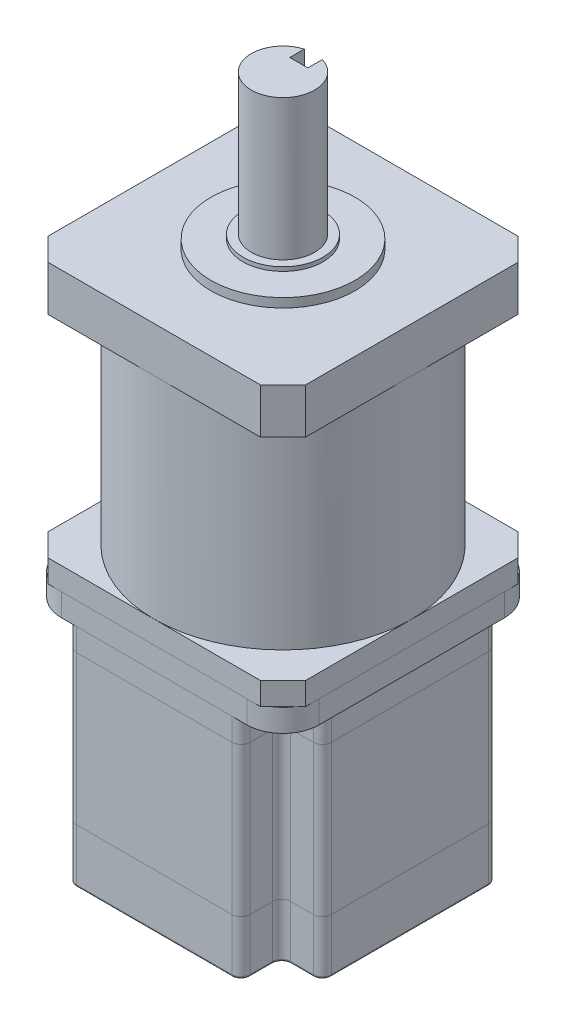
SolidWorks part; units mm, degrees
ref_plane "Front Plane" through (0, 0, 0) normal (0, 0, 1) x (1, 0, 0)
ref_plane "Top Plane" through (0, 0, 0) normal (0, 1, 0) x (1, 0, 0)
ref_plane "Right Plane" through (0, 0, 0) normal (1, 0, 0) x (0, 0, -1)
sketch "Sketch1" plane through (0, 0, 0) normal (0, 1, 0) x (1, 0, 0)
  circle A0 centre (0, 0) radius 28.5
  dimension "D1" = 57
extrude "Boss-Extrude1" add sketch "Sketch1" along normal blind 56.65
sketch "Sketch2" plane through (0, 0, 0) normal (0, -1, 0) x (1, 0, 0)
  line L1 (-28.5, 28.5) -> (28.5, 28.5)
  line L2 (-28.5, 28.5) -> (-28.5, -28.5)
  line L3 (-28.5, -28.5) -> (28.5, -28.5)
  line L4 (28.5, 28.5) -> (28.5, -28.5)
  line L5 (-28.5, 28.5) -> (28.5, -28.5) construction
  line L6 (-28.5, -28.5) -> (28.5, 28.5) construction
  point P0 (0, 0)
  dimension "D1" = 57
  dimension "D2" = 57
extrude "Boss-Extrude2" add sketch "Sketch2" along normal blind 5 separate body
chamfer "Chamfer1" distance 5 angle 45 4 edges at (28.5, -2.5, -28.5) (-28.5, -2.5, -28.5) (28.5, -2.5, 28.5) (-28.5, -2.5, 28.5)
sketch "Sketch3" plane through (0, -5, 0) normal (0, -1, 0) x (1, 0, 0)
  line L1 (-28.5, -28.5) -> (28.5, -28.5)
  line L2 (-28.5, -28.5) -> (-28.5, 28.5)
  line L3 (-28.5, 28.5) -> (28.5, 28.5)
  line L4 (28.5, -28.5) -> (28.5, 28.5)
  line L5 (-28.5, -28.5) -> (28.5, 28.5) construction
  line L6 (-28.5, 28.5) -> (28.5, -28.5) construction
  point P0 (0, 0)
  dimension "D1" = 57
  dimension "D2" = 57
extrude "Boss-Extrude3" add sketch "Sketch3" along normal blind 5 separate body
sketch "Sketch4" plane through (0, -10, 0) normal (0, -1, 0) x (1, 0, 0)
  line L0 (0, 28.5) -> (0, -28.5) construction
  line L1 (23.5, 28.5) -> (-23.5, 28.5) construction
  line L2 (-23.5, -28.5) -> (23.5, -28.5) construction
  line L3 (-28.5, 0) -> (28.5, 0) construction
  line L4 (-28.5, 23.5) -> (-28.5, -23.5) construction
  line L5 (28.5, -23.5) -> (28.5, 23.5) construction
  circle A0 centre (-23.5, 23.5) radius 2.5
  circle A1 centre (23.5, 23.5) radius 2.5
  circle A2 centre (23.5, -23.5) radius 2.5
  circle A3 centre (-23.5, -23.5) radius 2.5
  dimension "D1" = 5
  dimension "D2" = 5
  dimension "D3" = 5
  dimension "D4" = 5
  dimension "D7" = 23.5
  dimension "D8" = 23.5
  dimension "D9" = 23.5
  dimension "D10" = 23.5
  dimension "D11" = 23.5
  dimension "D12" = 23.5
  dimension "D5" = 23.5
  dimension "D6" = 23.5
extrude "Cut-Extrude1" cut sketch "Sketch4" against normal blind 15
sketch "Sketch6" plane through (0, -10, 0) normal (0, -1, 0) x (1, 0, 0)
  line L0 (28.5, 28.5) -> (-28.5, 28.5) construction
  line L1 (-19.2, 28.5) -> (19.2, 28.5)
  line L2 (-28.2, 19.5) -> (-28.2, -19.25)
  line L3 (-19.2, -28.25) -> (19.2, -28.25)
  line L4 (28.2, 19.5) -> (28.2, -19.25)
  line L9 (-28.2, 19.5) -> (-19.2, 19.5)
  line L10 (-19.2, 28.5) -> (-19.2, 19.5)
  line L11 (28.2, 19.5) -> (19.2, 19.5)
  line L12 (19.2, 28.5) -> (19.2, 19.5)
  line L15 (28.2, -19.25) -> (19.2, -19.25)
  line L16 (19.2, -28.25) -> (19.2, -19.25)
  line L19 (-28.2, -19.25) -> (-19.2, -19.25)
  line L20 (-19.2, -28.25) -> (-19.2, -19.25)
  dimension "D1" = 9
  dimension "D2" = 9
  dimension "D3" = 9
  dimension "D4" = 9
  dimension "D5" = 9
  dimension "D6" = 9
  dimension "D7" = 9
  dimension "D8" = 9
extrude "Boss-Extrude4" add sketch "Sketch6" along normal blind 5 separate body
sketch "Sketch7" plane through (0, -15, 0) normal (0, -1, 0) x (1, 0, 0)
  line L12 (19.2, 19.5) -> (19.2, 28.5)
  line L13 (19.2, 28.5) -> (-19.2, 28.5)
  line L14 (-19.2, 28.5) -> (-19.2, 19.5)
  line L15 (-19.2, 19.5) -> (-28.2, 19.5)
  line L16 (-28.2, 19.5) -> (-28.2, -19.25)
  line L17 (-28.2, -19.25) -> (-19.2, -19.25)
  line L18 (-19.2, -19.25) -> (-19.2, -28.25)
  line L19 (-19.2, -28.25) -> (19.2, -28.25)
  line L20 (19.2, -28.25) -> (19.2, -19.25)
  line L21 (19.2, -19.25) -> (28.2, -19.25)
  line L22 (28.2, -19.25) -> (28.2, 19.5)
  line L23 (28.2, 19.5) -> (19.2, 19.5)
  line L24 (19.2, 19.5) -> (19.2, 28.5)
  line L25 (19.2, 28.5) -> (-19.2, 28.5)
  line L26 (-19.2, 28.5) -> (-19.2, 19.5)
  line L27 (-19.2, 19.5) -> (-28.2, 19.5)
  line L28 (-28.2, 19.5) -> (-28.2, -19.25)
  line L29 (-28.2, -19.25) -> (-19.2, -19.25)
  line L30 (-19.2, -19.25) -> (-19.2, -28.25)
  line L31 (-19.2, -28.25) -> (19.2, -28.25)
  line L32 (19.2, -28.25) -> (19.2, -19.25)
  line L33 (19.2, -19.25) -> (28.2, -19.25)
  line L34 (28.2, -19.25) -> (28.2, 19.5)
  line L35 (28.2, 19.5) -> (19.2, 19.5)
  dimension "D1" = 0
extrude "Boss-Extrude5" add sketch "Sketch7" along normal blind 33 separate body
sketch "Sketch8" plane through (0, -48, 0) normal (0, -1, 0) x (1, 0, 0)
  line L12 (28.2, 19.5) -> (19.2, 19.5)
  line L13 (19.2, 19.5) -> (19.2, 28.5)
  line L14 (19.2, 28.5) -> (-19.2, 28.5)
  line L15 (-19.2, 28.5) -> (-19.2, 19.5)
  line L16 (-19.2, 19.5) -> (-28.2, 19.5)
  line L17 (-28.2, 19.5) -> (-28.2, -19.25)
  line L18 (-28.2, -19.25) -> (-19.2, -19.25)
  line L19 (-19.2, -19.25) -> (-19.2, -28.25)
  line L20 (-19.2, -28.25) -> (19.2, -28.25)
  line L21 (19.2, -28.25) -> (19.2, -19.25)
  line L22 (19.2, -19.25) -> (28.2, -19.25)
  line L23 (28.2, -19.25) -> (28.2, 19.5)
  line L24 (28.2, 19.5) -> (19.2, 19.5)
  line L25 (19.2, 19.5) -> (19.2, 28.5)
  line L26 (19.2, 28.5) -> (-19.2, 28.5)
  line L27 (-19.2, 28.5) -> (-19.2, 19.5)
  line L28 (-19.2, 19.5) -> (-28.2, 19.5)
  line L29 (-28.2, 19.5) -> (-28.2, -19.25)
  line L30 (-28.2, -19.25) -> (-19.2, -19.25)
  line L31 (-19.2, -19.25) -> (-19.2, -28.25)
  line L32 (-19.2, -28.25) -> (19.2, -28.25)
  line L33 (19.2, -28.25) -> (19.2, -19.25)
  line L34 (19.2, -19.25) -> (28.2, -19.25)
  line L35 (28.2, -19.25) -> (28.2, 19.5)
  dimension "D1" = 0
extrude "Boss-Extrude6" add sketch "Sketch8" along normal blind 12 separate body
fillet "Fillet1" radius 2 12 edges at (19.2, -12.5, -19.25) (19.2, -12.5, -28.25) (-19.2, -12.5, -28.25) (-19.2, -12.5, -19.25) (-28.2, -12.5, -19.25) (-28.2, -12.5, 19.5) (-19.2, -12.5, 19.5) (-19.2, -12.5, 28.5) (28.2, -12.5, -19.25) (19.2, -12.5, 19.5) (19.2, -12.5, 28.5) (28.2, -12.5, 19.5)
fillet "Fillet2" radius 2 12 edges at (-19.2, -31.5, -28.25) (-19.2, -31.5, -19.25) (-28.2, -31.5, -19.25) (-28.2, -31.5, 19.5) (-19.2, -31.5, 19.5) (-19.2, -31.5, 28.5) (19.2, -31.5, 28.5) (19.2, -31.5, 19.5) (28.2, -31.5, 19.5) (28.2, -31.5, -19.25) (19.2, -31.5, -19.25) (19.2, -31.5, -28.25)
fillet "Fillet3" radius 2 12 edges at (-28.2, -54, 19.5) (-19.2, -54, 19.5) (-19.2, -54, 28.5) (19.2, -54, 28.5) (19.2, -54, 19.5) (28.2, -54, 19.5) (28.2, -54, -19.25) (19.2, -54, -19.25) (19.2, -54, -28.25) (-19.2, -54, -28.25) (-19.2, -54, -19.25) (-28.2, -54, -19.25)
fillet "Fillet4" radius 0.5 24 edges at (-19.7858, -60, 20.0858) (-19.2, -60, 24) (-18.6142, -60, 27.9142) (0, -60, 28.5) (18.6142, -60, 27.9142) (19.2, -60, 24) (19.7858, -60, 20.0858) (23.7, -60, 19.5) (27.6142, -60, 18.9142) (28.2, -60, 0.125) (27.6142, -60, -18.6642) (23.7, -60, -19.25) (19.7858, -60, -19.8358) (19.2, -60, -23.75) (18.6142, -60, -27.6642) (0, -60, -28.25) (-18.6142, -60, -27.6642) (-19.2, -60, -23.75) (-19.7858, -60, -19.8358) (-23.7, -60, -19.25) (-27.6142, -60, -18.6642) (-28.2, -60, 0.125) (-27.6142, -60, 18.9142) (-23.7, -60, 19.5)
fillet "Fillet5" radius 8 4 edges at (-28.5, -7.5, -28.5) (-28.5, -7.5, 28.5) (28.5, -7.5, -28.5) (28.5, -7.5, 28.5)
sketch "Sketch9" plane through (0, 56.65, 0) normal (0, 1, 0) x (1, 0, 0)
  circle A0 centre (0, 0) radius 15.95
  dimension "D1" = 31.9
extrude "Boss-Extrude7" add sketch "Sketch9" along normal blind 2
sketch "Sketch10" plane through (0, 58.65, 0) normal (0, 1, 0) x (1, 0, 0)
  circle A0 centre (0, 0) radius 8.85
  dimension "D1" = 17.7
extrude "Boss-Extrude8" add sketch "Sketch10" along normal blind 0.9 separate body
sketch "Sketch11" plane through (0, 59.55, 0) normal (0, 1, 0) x (1, 0, 0)
  circle A0 centre (0, 0) radius 7
  dimension "D1" = 14
extrude "Boss-Extrude9" add sketch "Sketch11" along normal blind 31.1 separate body
sketch "Sketch12" plane through (0, 90.65, 0) normal (0, 1, 0) x (1, 0, 0)
  line L0 (0, 0) -> (0, 12.8742) construction
  line L1 (3.6056, -6) -> (11.1303, -6) construction
  line L2 (-2, 3.5) -> (2, 3.5)
  line L3 (-2, 3.5) -> (-2, 8.6117)
  line L4 (-2, 8.6117) -> (2, 8.6117)
  line L5 (2, 3.5) -> (2, 8.6117)
  line L6 (-2, 3.5) -> (2, 8.6117) construction
  line L7 (-2, 8.6117) -> (2, 3.5) construction
  circle A0 centre (0, 0) radius 7 construction
  point P3 (0, 6.0558)
  dimension "D2" = 9.5
  dimension "D1" = 4
extrude "Cut-Extrude2" cut sketch "Sketch12" against normal blind 20
fillet "Fillet6" radius 2 2 edges at (-2, 70.65, -5.1041) (2, 70.65, -5.1041)
sketch "Sketch13" plane through (0, 56.65, 0) normal (0, 1, 0) x (1, 0, 0)
  line L8 (28.5, -23.5) -> (28.5, 23.5)
  line L9 (28.5, 23.5) -> (23.5, 28.5)
  line L10 (23.5, 28.5) -> (-23.5, 28.5)
  line L11 (-23.5, 28.5) -> (-28.5, 23.5)
  line L12 (-28.5, 23.5) -> (-28.5, -23.5)
  line L13 (-28.5, -23.5) -> (-23.5, -28.5)
  line L14 (-23.5, -28.5) -> (23.5, -28.5)
  line L15 (23.5, -28.5) -> (28.5, -23.5)
  line L16 (28.5, -23.5) -> (28.5, 23.5)
  line L17 (28.5, 23.5) -> (23.5, 28.5)
  line L18 (23.5, 28.5) -> (-23.5, 28.5)
  line L19 (-23.5, 28.5) -> (-28.5, 23.5)
  line L20 (-28.5, 23.5) -> (-28.5, -23.5)
  line L21 (-28.5, -23.5) -> (-23.5, -28.5)
  line L22 (-23.5, -28.5) -> (23.5, -28.5)
  line L23 (23.5, -28.5) -> (28.5, -23.5)
  dimension "D1" = 0
extrude "Boss-Extrude10" add sketch "Sketch13" against normal blind 10
sketch "Sketch14" [suppressed] plane through (0, 56.65, 0) normal (0, 1, 0) x (1, 0, 0)
  line L1 (-23.57, -23.57) -> (23.57, -23.57) construction
  line L2 (-23.57, -23.57) -> (-23.57, 23.57) construction
  line L3 (-23.57, 23.57) -> (23.57, 23.57) construction
  line L4 (23.57, -23.57) -> (23.57, 23.57) construction
  line L5 (-23.57, -23.57) -> (23.57, 23.57) construction
  line L6 (-23.57, 23.57) -> (23.57, -23.57) construction
  circle A0 centre (23.57, 23.57) radius 2.6
  circle A1 centre (23.57, -23.57) radius 2.6
  circle A2 centre (-23.57, -23.57) radius 2.6
  circle A3 centre (-23.57, 23.57) radius 2.6
  point P0 (0, 0)
  dimension "D3" = 5.2
  dimension "D4" = 5.2
  dimension "D5" = 5.2
  dimension "D6" = 5.2
  dimension "D1" = 47.14
  dimension "D2" = 47.14
extrude "Cut-Extrude3" [suppressed] cut sketch "Sketch14" against normal up to next
